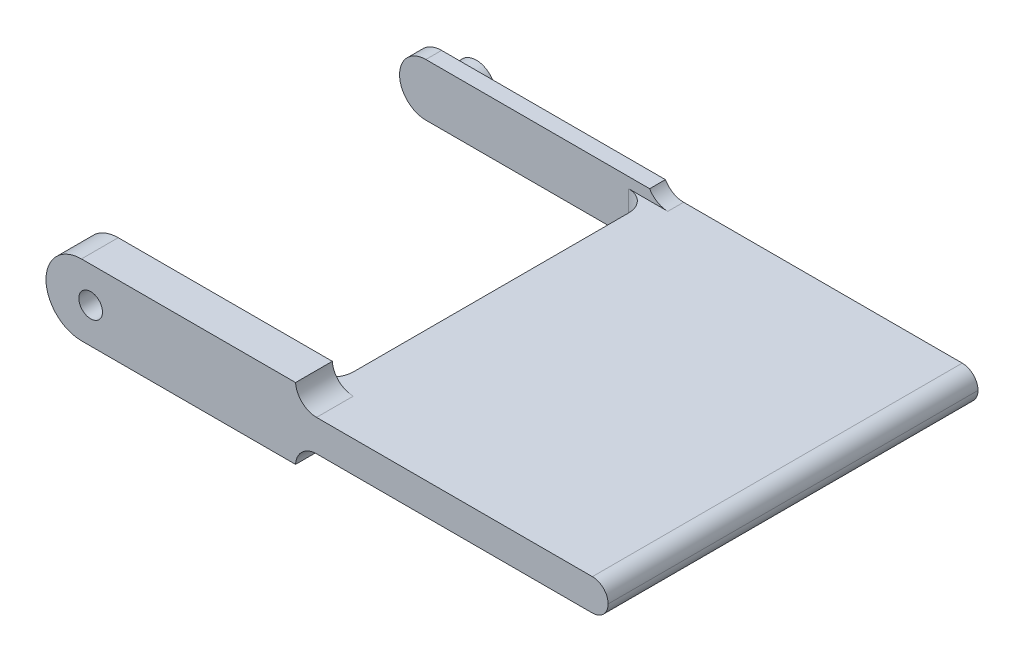
SolidWorks part; units mm, degrees
ref_plane "Front Plane" through (0, 0, 0) normal (0, 0, 1) x (1, 0, 0)
ref_plane "Top Plane" through (0, 0, 0) normal (0, 1, 0) x (1, 0, 0)
ref_plane "Right Plane" through (0, 0, 0) normal (1, 0, 0) x (0, 0, -1)
ref_plane "TopPlane" through (0, 0, 33.2) normal (0, 0, 1) x (1, 0, 0)
sketch "Sketch1" plane through (0, 0, 33.2) normal (0, 0, 1) x (1, 0, 0)
  line L1 (0, 0) -> (0, 3) construction
  line L3 (-4.25, -3.375) -> (19.5, -3.375)
  line L4 (12.065, -1.635) -> (0, -1.635)
  line L5 (-4.25, -3.375) -> (-4.25, 3.375)
  line L6 (-4.25, 3.375) -> (19.5, 3.375)
  line L8 (19.5, -3.375) -> (19.5, 3.375)
  line L11 (12.065, -1.635) -> (12.065, 1.635)
  line L13 (19.5, 1.5) -> (49.25, 1.5)
  line L15 (19.5, -1.5) -> (49.25, -1.5)
  line L16 (49.25, 1.5) -> (49.25, -1.5)
  line L22 (12.065, 1.635) -> (0, 1.635)
  line L23 (0, -1.635) -> (0, 1.635)
  circle A0 centre (0, 0) radius 3
  circle A1 centre (0, 0) radius 1.125
  arc A2 (12.065, 1.635) -> (12.065, -1.635) centre (12.065, 0) cw
  point P8 (0, 0)
  point P10 (-4.25, 0)
  point P12 (0, 0)
  point P19 (19.5, 0)
  point P22 (13.7, 0)
  point P27 (0, 6.75)
  point P35 (49.25, 0)
  dimension "D1" = 6
  dimension "D9" = 2.25
  dimension "D2" = 19.5
  dimension "D3" = 3
  dimension "D4" = 29.75
  dimension "D5" = 4.25
  dimension "D6" = 6.75
  dimension "D7" = 3.27
  dimension "D8" = 13.7
extrude "Boss-Extrude10" add sketch "Sketch1" along normal blind 2 contours L3 L8 L6 L5 L22 A2 L4 A0 | A0 L4 L11 L22 | A2 L11 | L23 L1 A0 L4 A1 | A1 L23 L4 A0 L22 | L1 L22 A0 region at (-0.0815, 1.38, 33.2) region at (1.6834, 0, 33.2) region at (0.9803, 2.1933, 33.2) region at (7.4534, 0, 33.2) region at (12.7589, 0, 33.2) region at (-4.0031, 0, 33.2)
extrude "Boss-Extrude15" add sketch "Sketch1<16>" against normal blind 1.5 contours L3 L8 L6 L5 L22 A2 L4 A0
sketch "Sketch1<16>" plane through (0, 0, 33.2) normal (0, 0, 1) x (1, 0, 0) same geometry as "Sketch1"
extrude "Boss-Extrude17" add sketch "Sketch1<17>" along direction (0, 0, 1) on the side against the normal up to surface (33.2 mm away) from surface contours L13 L15 L16 region at (34.375, 0, 33.2) up to plane "Front Plane" starting at face at (1.125, 0, 35.2)
sketch "Sketch1<17>" plane through (0, 0, 33.2) normal (0, 0, 1) x (1, 0, 0) same geometry as "Sketch1"
sketch "Sketch2" plane through (0, 0, 0) normal (0, 0, -1) x (-1, 0, 0)
  line L0 (-19.5, -1.5) -> (-19.5, 1.5) construction
  line L2 (4.3, -2.5) -> (-19.5, -2.5)
  line L3 (4.3, 2.5) -> (-19.5, 2.5)
  line L4 (4.3, 2.5) -> (4.3, -2.5)
  line L5 (-19.5, 2.5) -> (-19.5, -2.5)
  point P4 (-19.5, 0)
  point P6 (-19.5, 0)
  dimension "D1" = 5
  dimension "D2" = 4.3
extrude "Boss-Extrude18" add sketch "Sketch2" against normal blind 1.5 contours L2 L5 L3 L4 | L4 L2 L5 L3 region at (7.6, 0, 0)
fillet "Fillet1" radius 2 4 edges at (19.5, -1.5, 0.75) (19.5, 1.5, 0.75)
fillet "Fillet3" radius 2 2 edges at (19.5, 0, 1.5) (19.5, 0, 31.7)
fillet "Fillet2" radius 3.375 2 edges at (-4.25, 3.375, 33.45) (-4.25, -3.375, 33.45)
fillet "Fillet5" radius 2.5 2 edges at (-4.3, -2.5, 0.75) (-4.3, 2.5, 0.75)
sketch "Sketch4" plane through (0, 0, 0) normal (0, 0, -1) x (-1, 0, 0)
  circle A0 centre (0, 0) radius 1.85
  dimension "D1" = 3.7
extrude "Boss-Extrude19" add sketch "Sketch4" along normal blind 1.5 contours A0
fillet "Fillet4" radius 1.5 2 edges at (49.25, 1.5, 17.6) (49.25, -1.5, 17.6)
sketch3d "URDF Reference"
  line L0 (0, 0, 0) -> (10, 0, 0) construction
  line L1 (0, 0, 0) -> (0, 0, -10) construction
  point P0 (0, 0, 0)
  point P1 (0, 0, 0)
